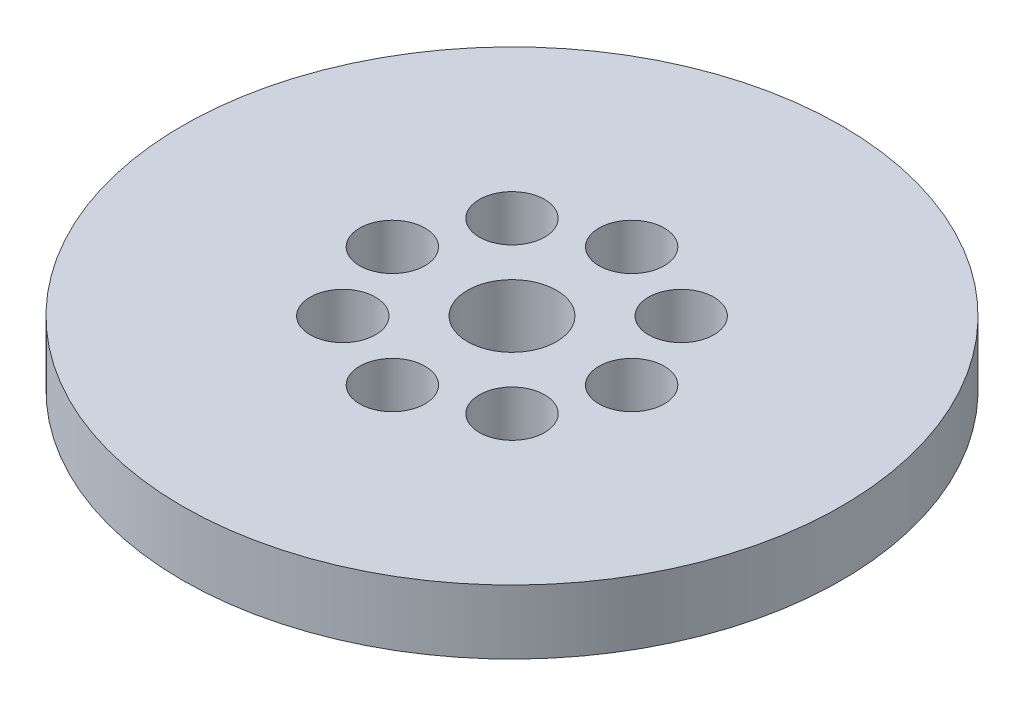
SolidWorks part; units mm, degrees
ref_plane "Front Plane" through (0, 0, 0) normal (0, 0, 1) x (1, 0, 0)
ref_plane "Top Plane" through (0, 0, 0) normal (0, 1, 0) x (1, 0, 0)
ref_plane "Right Plane" through (0, 0, 0) normal (1, 0, 0) x (0, 0, -1)
sketch "Sketch1" plane through (0, 0, 0) normal (0, 1, 0) x (1, 0, 0)
  circle A0 centre (0, 0) radius 92.5
  dimension "FLANGE_OD" = 185
extrude "Boss-Extrude1" add sketch "Sketch1" along normal blind 18
sketch "Sketch2" plane through (0, 0, 0) normal (0, 1, 0) x (1, 0, 0)
  circle A0 centre (0, 0) radius 12.5
  dimension "BORE_D" = 25
extrude "Cut-Extrude1" cut sketch "Sketch2" along normal through all
sketch "Sketch3" plane through (0, 18, 0) normal (0, 1, 0) x (1, 0, 0)
  circle A0 centre (0, 0) radius 33.5814 construction
  circle A1 centre (-33.5814, 0) radius 9.1729
  dimension "BOLT_D" = 18.3459
  dimension "BOLT_PCD" = 67.1628
extrude "Cut-Extrude2" cut sketch "Sketch3" against normal blind 17.5212
pattern_circular "CirPattern1" count 8 over 360 about axis through (0, 0, 0) along (0, 1, 0) of "Cut-Extrude2"
